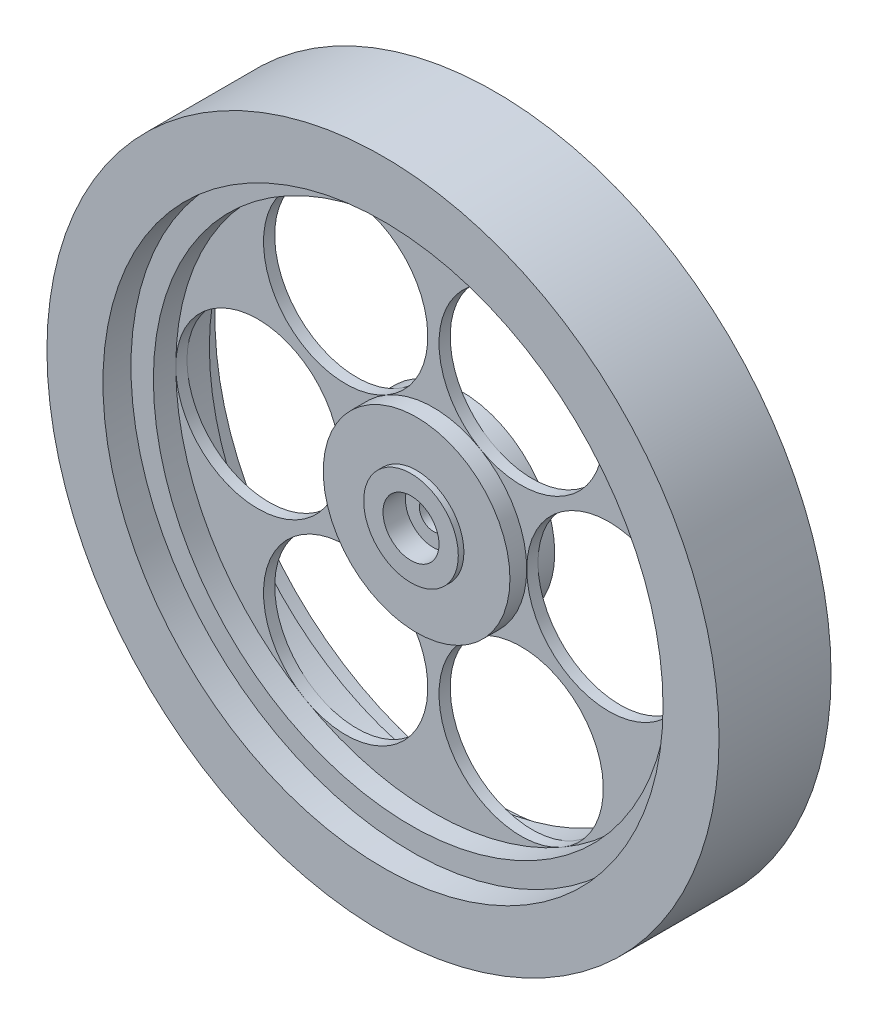
SolidWorks part; units mm, degrees
material "1060 Alloy"
ref_plane "Front Plane" through (0, 0, 0) normal (0, 0, 1) x (1, 0, 0)
ref_plane "Top Plane" through (0, 0, 0) normal (0, 1, 0) x (1, 0, 0)
ref_plane "Right Plane" through (0, 0, 0) normal (1, 0, 0) x (0, 0, -1)
sketch "Sketch1" plane through (0, 0, 0) normal (0, 0, 1) x (1, 0, 0)
  line L0 (0, 0) -> (38.1, 0) construction
  line L1 (0, 0) -> (19.05, 32.9956) construction
  line L2 (0, 0) -> (-14.605, 25.2966) construction
  line L3 (0, 0) -> (14.605, -25.2966) construction
  line L4 (0, 0) -> (-14.605, -25.2966) construction
  circle A0 centre (0, 0) radius 38.1
  circle A1 centre (0, 0) radius 31.75
  circle A2 centre (0, 0) radius 3.175
  circle A3 centre (0, 0) radius 5.364
  circle A4 centre (0, 0) radius 10.5833
  circle A5 centre (0, 0) radius 29.21
  circle A6 centre (19.8967, 0) radius 9.3133
  circle A7 centre (9.9483, 17.231) radius 9.3133
  circle A8 centre (-9.9483, 17.231) radius 9.3133
  circle A9 centre (-19.8967, 0) radius 9.3133
  circle A10 centre (-9.9483, -17.231) radius 9.3133
  circle A11 centre (9.9483, -17.231) radius 9.3133
  circle A12 centre (0, 0) radius 1.5875
  dimension "D1" = 76.2
  dimension "D2" = 6.35
  dimension "D3" = 2.54
  dimension "D4" = 6.35
  dimension "D5" = 60
  dimension "D7" = 3.175
  dimension "D8" = 1.27
  dimension "D6" = 120
extrude "Boss-Extrude1" add sketch "Sketch1" along normal mid plane 1.27 contours A2 | A8 A4 A7 A5 | A9 A4 A8 A5 | A10 A4 A9 A5 | A11 A4 A10 A5 | A11 A5 A6 A4 | A7 A4 A6 A5 region at (-3.0852, 0, 0) region at (20.0653, -11.5847, 0) region at (20.0653, 11.5847, 0) region at (0, 23.1695, 0) region at (0, -23.1695, 0) region at (-20.0653, 11.5847, 0) region at (-20.0653, -11.5847, 0)
extrude "Boss-Extrude2" add sketch "Sketch1<3>" along normal mid plane 6.35 contours A3 A2 | A1 A5 region at (-30.852, 0, 0) region at (-5.2122, 0, 0)
sketch "Sketch1<3>" plane through (0, 0, 0) normal (0, 0, 1) x (1, 0, 0) same geometry as "Sketch1"
extrude "Boss-Extrude4" add sketch "Sketch1<4>" along normal mid plane 5.08 contours A4 A3 region at (8.9062, -5.142, 0)
sketch "Sketch1<4>" plane through (0, 0, 0) normal (0, 0, 1) x (1, 0, 0) same geometry as "Sketch1"
extrude "Boss-Extrude5" add sketch "Sketch1<5>" along normal mid plane 12.7 contours A0 A1 region at (-37.0224, 0, 0)
sketch "Sketch1<5>" plane through (0, 0, 0) normal (0, 0, 1) x (1, 0, 0) same geometry as "Sketch1"
